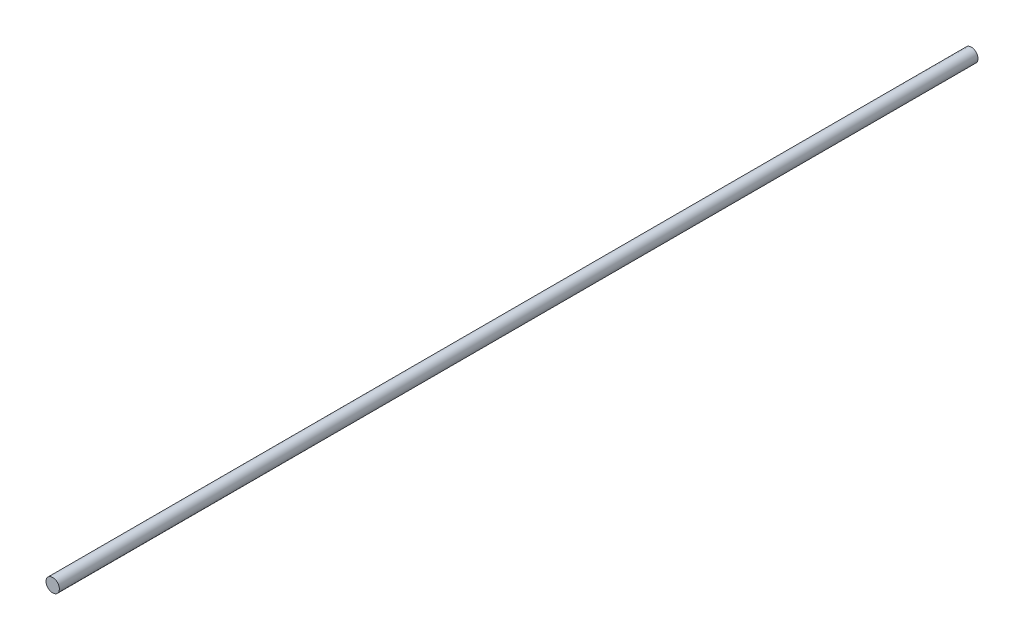
SolidWorks part; units mm, degrees
material "1.7244 (18CrMoS4)"
ref_plane "Přední rovina" through (0, 0, 0) normal (0, 0, 1) x (1, 0, 0)
ref_plane "Horní rovina" through (0, 0, 0) normal (0, 1, 0) x (1, 0, 0)
ref_plane "Pravá rovina" through (0, 0, 0) normal (1, 0, 0) x (0, 0, -1)
sketch "Skica1" plane through (0, 0, 0) normal (0, 0, 1) x (1, 0, 0)
  circle A0 centre (0, 0) radius 4
  dimension "D1" = 8
extrude "Přidat vysunutím1" add sketch "Skica1" along normal blind 550
